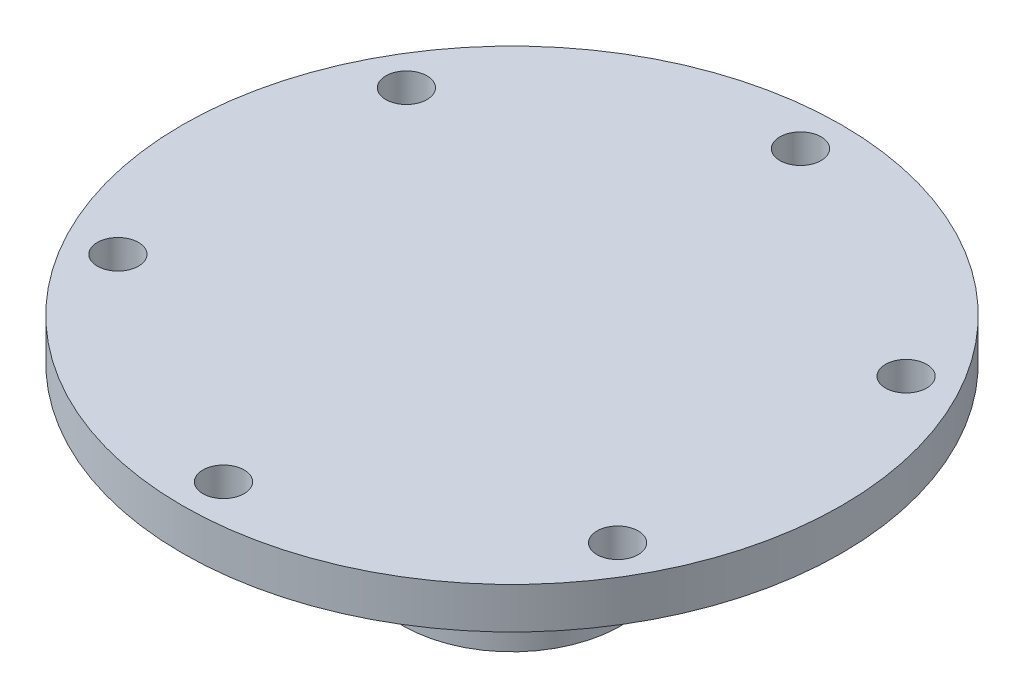
SolidWorks part; units mm, degrees
ref_plane "Front Plane" through (0, 0, 0) normal (0, 0, 1) x (1, 0, 0)
ref_plane "Top Plane" through (0, 0, 0) normal (0, 1, 0) x (1, 0, 0)
ref_plane "Right Plane" through (0, 0, 0) normal (1, 0, 0) x (0, 0, -1)
ref_axis "Centerline" through (0, 21.4963, 0) along (0, -1, 0)
sketch "Sketch1" plane through (0, 0, 0) normal (0, 1, 0) x (1, 0, 0)
  circle A0 centre (0, 0) radius 20.32
  dimension "D1" = 40.64
extrude "Cylinder" add sketch "Sketch1" along normal blind 14.478
sketch "Sketch2" plane through (0, 0, 0) normal (0, 0, 1) x (1, 0, 0)
  line L0 (0, 20.1077) -> (0, -7.6632) construction
  line L1 (20.32, 0) -> (12.7, 0)
  line L2 (20.32, 0) -> (20.32, 11.938)
  line L3 (20.32, 11.938) -> (12.7, 11.938)
  line L4 (12.7, 0) -> (12.7, 11.938)
  line L5 (20.32, 14.478) -> (-20.32, 14.478) construction
  dimension "D1" = 12.7
  dimension "D2" = 2.54
revolve "Mid O Ring Wings" cut sketch "Sketch2" angle 360 about axis through (0, 21.4963, 0) along (0, -1, 0)
sketch "Sketch3" plane through (0, 0, 0) normal (0, 0, 1) x (1, 0, 0)
  line L0 (12.7, 0) -> (12.7, 11.938) construction
  line L1 (12.7, 10.668) -> (10.414, 10.668)
  line L2 (12.7, 10.668) -> (12.7, 7.874)
  line L3 (12.7, 7.874) -> (10.414, 7.874)
  line L4 (10.414, 10.668) -> (10.414, 7.874)
  line L5 (-12.7, 11.938) -> (12.7, 11.938) construction
  dimension "D1" = 1.27
  dimension "D2" = 2.286
  dimension "D3" = 2.794
revolve "Mid O Ring Cut" cut sketch "Sketch3" angle 360 about axis through (0, 21.4963, 0) along (0, -1, 0)
sketch "Sketch4" plane through (0, 0, 0) normal (0, 0, 1) x (1, 0, 0)
  line L0 (12.7, 7.874) -> (-12.7, 7.874) construction
  line L1 (12.7, 0) -> (6.731, 0)
  line L2 (12.7, 0) -> (12.7, 6.604)
  line L3 (12.7, 6.604) -> (6.731, 6.604)
  line L4 (6.731, 0) -> (6.731, 6.604)
  line L5 (0, 20.9905) -> (0, -6.9276) construction
  dimension "D1" = 1.27
  dimension "D2" = 6.731
revolve "Bottom O Ring Wings" cut sketch "Sketch4" angle 360 about axis through (0, 21.4963, 0) along (0, -1, 0)
sketch "Sketch5" plane through (0, 0, 0) normal (0, 0, 1) x (1, 0, 0)
  line L0 (6.731, 0) -> (6.731, 6.604) construction
  line L1 (6.731, 5.334) -> (4.445, 5.334)
  line L2 (6.731, 5.334) -> (6.731, 2.54)
  line L3 (6.731, 2.54) -> (4.445, 2.54)
  line L4 (4.445, 5.334) -> (4.445, 2.54)
  line L5 (-6.731, 6.604) -> (6.731, 6.604) construction
  dimension "D1" = 1.27
  dimension "D2" = 2.794
  dimension "D3" = 2.286
revolve "Bottom O Ring Cut" cut sketch "Sketch5" angle 360 about axis through (0, 21.4963, 0) along (0, -1, 0)
chamfer "Bottom Chamfer" distance 6.731 distance2 1.27 1 edges at (0, 0, 6.731) first distance on face at (0, 0, 6.731)
sketch "Sketch6" plane through (0, 14.478, 0) normal (0, 1, 0) x (1, 0, 0)
  circle A0 centre (0, 17.78) radius 1.27
  circle A1 centre (0, 0) radius 20.32 construction
  dimension "D1" = 2.54
  dimension "D2" = 17.78
extrude "Mounting Hole" cut sketch "Sketch6" against normal up to next
pattern_circular "Mounting Hole Pattern" count 6 over 360 about axis through (0, 14.478, 0) along (0, 1, 0) of "Mounting Hole"
